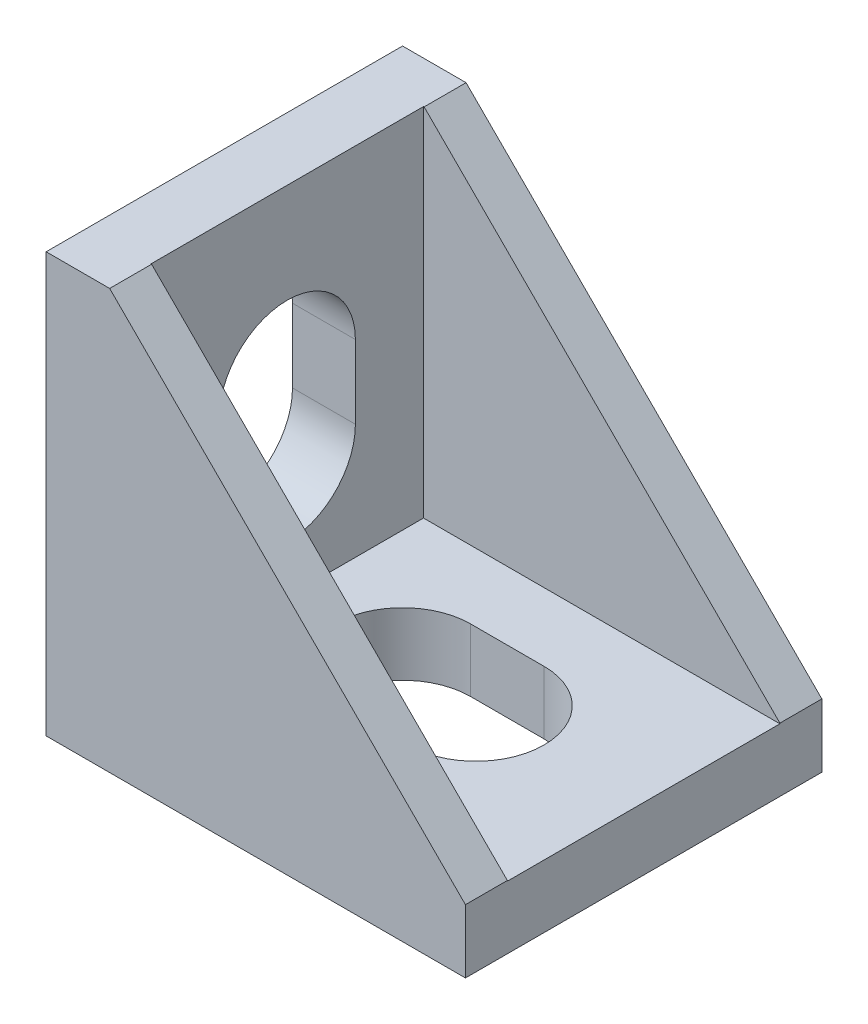
SolidWorks part; units mm, degrees
ref_plane "Front Plane" through (0, 0, 0) normal (0, 0, 1) x (1, 0, 0)
ref_plane "Top Plane" through (0, 0, 0) normal (0, 1, 0) x (1, 0, 0)
ref_plane "Right Plane" through (0, 0, 0) normal (1, 0, 0) x (0, 0, -1)
sketch "Sketch1" plane through (0, 0, 0) normal (0, 0, 1) x (1, 0, 0)
  line L0 (0, 0) -> (0, 20)
  line L1 (0, -55) -> (0, 55) construction
  line L2 (0, 20) -> (3.0294, 20)
  line L3 (3.0294, 20) -> (20, 3.0294)
  line L4 (20, 3.0294) -> (20, 0)
  line L5 (55, 0) -> (-55, 0) construction
  line L6 (20, 0) -> (0, 0)
  dimension "D1" = 24
  dimension "D2" = 20
  dimension "D3" = 20
extrude "Boss-Extrude1" add sketch "Sketch1" along normal blind 17
ref_plane "Plane1" through (0, 0, 2) normal (0, 0, 1) x (1, 0, 0)
sketch "Sketch2" plane through (0, 0, 2) normal (0, 0, 1) x (1, 0, 0)
  line L0 (0, -9.35) -> (0, 9.35) construction
  line L1 (3, 3) -> (20, 3)
  line L2 (3, 3) -> (3, 20)
  line L3 (3, 20) -> (20, 20)
  line L4 (20, 3) -> (20, 20)
  line L5 (9.35, 0) -> (-9.35, 0) construction
  dimension "D1" = 17
  dimension "D2" = 17
  dimension "D3" = 3
  dimension "D4" = 3
extrude "Cut-Extrude1" cut sketch "Sketch2" along normal blind 13
sketch "Sketch3" plane through (0, 0, 0) normal (0, 1, 0) x (1, 0, 0)
  line L0 (8.5, -8.5) -> (12, -8.5) construction
  line L1 (8.5, -5.25) -> (12, -5.25)
  line L3 (8.5, -11.75) -> (12, -11.75)
  line L5 (-11, 0) -> (11, 0) construction
  line L6 (20, -17) -> (3.0294, -17) construction
  line L11 (0, -9.35) -> (0, 9.35) construction
  arc A0 (8.5, -5.25) -> (8.5, -11.75) centre (8.5, -8.5) ccw
  arc A1 (12, -11.75) -> (12, -5.25) centre (12, -8.5) ccw
  point P2 (10.25, -8.5)
  dimension "D2" = 3.5
  dimension "D3" = 8.5
  dimension "D1" = 6.5
extrude "Cut-Extrude2" cut sketch "Sketch3" along normal blind 13
sketch "Sketch6" plane through (0, 0, 0) normal (1, 0, 0) x (0, 0, -1)
  line L0 (-17, 20) -> (0, 20) construction
  line L1 (-6.5, 19) -> (-10, 19)
  line L2 (-6.5, 19) -> (-6.5, 17.5)
  line L3 (-6.5, 17.5) -> (-10, 17.5)
  line L4 (-10, 19) -> (-10, 17.5)
  line L5 (-6.5, 3.5) -> (-10, 3.5)
  line L6 (-6.5, 3.5) -> (-6.5, 2)
  line L7 (-6.5, 2) -> (-10, 2)
  line L8 (-10, 3.5) -> (-10, 2)
  line L9 (11.55, 0) -> (-11.55, 0) construction
  line L10 (0, 11.55) -> (0, -11.55) construction
  dimension "D1" = 1.5
  dimension "D2" = 3.5
  dimension "D3" = 1
  dimension "D4" = 2
  dimension "D5" = 6.5
extrude "Boss-Extrude2" add sketch "Sketch6" against normal blind 1
fillet "Fillet1" radius 0.75 8 edges at (-0.5, 2, 6.5) (-0.5, 17.5, 6.5) (-0.5, 2, 10) (-0.5, 3.5, 10) (-0.5, 3.5, 6.5) (-0.5, 17.5, 10) (-0.5, 19, 10) (-0.5, 19, 6.5)
sketch "Sketch7" plane through (0, 0, 0) normal (0, 1, 0) x (1, 0, 0)
  line L0 (0, -17.4625) -> (0, 17.4625) construction
  line L1 (2, -6.5) -> (2, -10)
  line L2 (2, -6.5) -> (3.5, -6.5)
  line L3 (3.5, -6.5) -> (3.5, -10)
  line L4 (2, -10) -> (3.5, -10)
  line L5 (17.5, -6.5) -> (17.5, -10)
  line L6 (17.5, -6.5) -> (19, -6.5)
  line L7 (19, -6.5) -> (19, -10)
  line L8 (17.5, -10) -> (19, -10)
  line L9 (20, -15) -> (20, -2) construction
  line L11 (-11.55, 0) -> (11.55, 0) construction
  dimension "D1" = 1.5
  dimension "D2" = 3.5
  dimension "D3" = 2
  dimension "D4" = 1
  dimension "D5" = 6.5
extrude "Boss-Extrude3" add sketch "Sketch7" against normal blind 1
fillet "Fillet2" radius 0.75 8 edges at (3.5, -0.5, 6.5) (2, -0.5, 6.5) (2, -0.5, 10) (3.5, -0.5, 10) (17.5, -0.5, 10) (19, -0.5, 10) (17.5, -0.5, 6.5) (19, -0.5, 6.5)
sketch "Sketch8" plane through (0, 0, 0) normal (1, 0, 0) x (0, 0, -1)
  line L0 (-17, 3.0294) -> (-17, 20) construction
  line L2 (-8.5, 8.5) -> (-8.5, 12) construction
  line L4 (-11.75, 8.5) -> (-11.75, 12)
  line L5 (-5.25, 8.5) -> (-5.25, 12)
  line L6 (9.35, 0) -> (-9.35, 0) construction
  line L7 (0, 11.55) -> (0, -11.55) construction
  arc A2 (-11.75, 8.5) -> (-5.25, 8.5) centre (-8.5, 8.5) ccw
  arc A3 (-5.25, 12) -> (-11.75, 12) centre (-8.5, 12) ccw
  point P7 (-8.5, 10.25)
  dimension "D3" = 3.5
  dimension "D4" = 6.5
  dimension "D5" = 8.5
extrude "Cut-Extrude3" cut sketch "Sketch8" along normal blind 10
